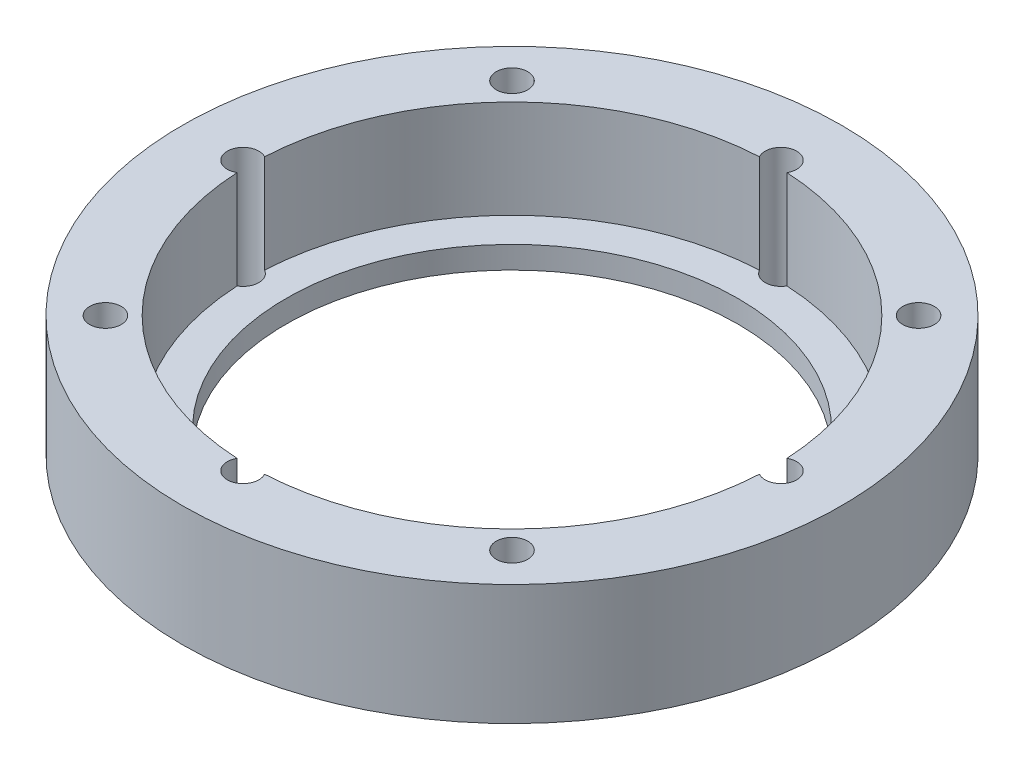
SolidWorks part; units mm, degrees
ref_plane "Front Plane" through (0, 0, 0) normal (0, 0, 1) x (1, 0, 0)
ref_plane "Top Plane" through (0, 0, 0) normal (0, 1, 0) x (1, 0, 0)
ref_plane "Right Plane" through (0, 0, 0) normal (1, 0, 0) x (0, 0, -1)
sketch "Sketch1" plane through (0, 0, 0) normal (0, 0, 1) x (1, 0, 0)
  line L0 (-23.5, 8.5875) -> (-18.65, 8.5875)
  line L1 (-18.65, 8.5875) -> (-18.65, 1.5875)
  line L2 (-18.65, 1.5875) -> (-16.11, 1.5875)
  line L3 (-16.11, 1.5875) -> (-16.11, 0)
  line L4 (-16.11, 0) -> (-23.5, 0)
  line L5 (-23.5, 0) -> (-23.5, 8.5875)
  line L6 (0, 0) -> (0, 10.8043) construction
  line L7 (-16.11, 0) -> (0, 0) construction
  dimension "D1" = 37.3
  dimension "D2" = 2.54
  dimension "D3" = 7
  dimension "D4" = 1.5875
  dimension "D5" = 47
revolve "Revolve1" add sketch "Sketch1" angle 360 about L6
sketch "Sketch2" plane through (0, 0, 0) normal (0, -1, 0) x (-1, 0, 0)
  line L0 (19.177, 0) -> (0, 0) construction
  circle A0 centre (19.177, 0) radius 1.125
  dimension "D2" = 2.25
  dimension "D1" = 19.177
extrude "Cut-Extrude1" cut sketch "Sketch2" against normal through all
ref_axis "Axis1" through (0, 8.5875, 0) along (0, -1, 0)
sketch "Sketch3" plane through (0, 0, 0) normal (0, -1, 0) x (1, 0, 0)
  line L0 (0, 0) -> (-14.4957, 14.4957) construction
  line L1 (-14.4957, 14.4957) -> (0, 14.4957) construction
  line L2 (0, 14.4957) -> (0, 0) construction
  circle A0 centre (-14.4957, 14.4957) radius 1.125
  circle A1 centre (-19.177, 0) radius 1.125 construction
  dimension "D1" = 20.5
extrude "Cut-Extrude2" cut sketch "Sketch3" against normal through all
pattern_circular "CirPattern1" count 4 over 360 about axis through (0, 8.5875, 0) along (0, -1, 0) of "Cut-Extrude1", "Cut-Extrude2"
